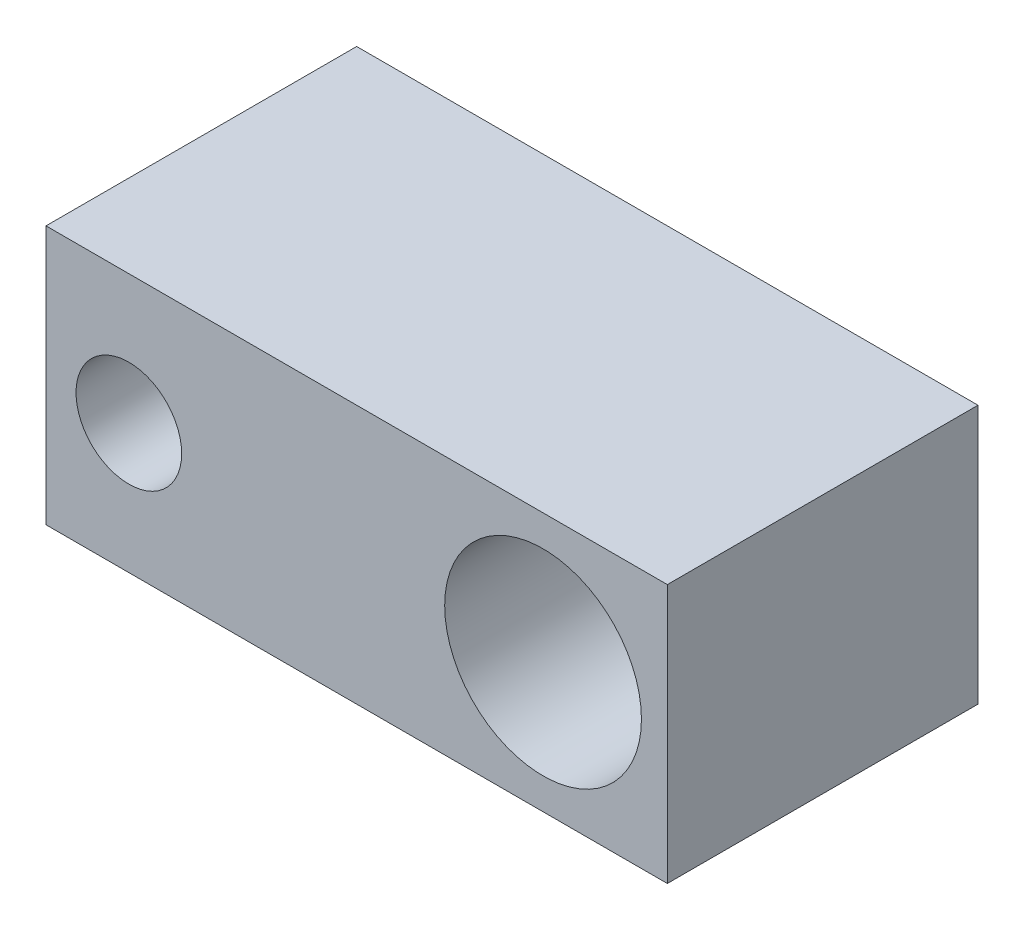
SolidWorks part; units mm, degrees
ref_plane "Front Plane" through (0, 0, 0) normal (0, 0, 1) x (1, 0, 0)
ref_plane "Top Plane" through (0, 0, 0) normal (0, 1, 0) x (1, 0, 0)
ref_plane "Right Plane" through (0, 0, 0) normal (1, 0, 0) x (0, 0, -1)
sketch "Sketch1" plane through (0, 0, 0) normal (0, 0, 1) x (1, 0, 0)
  line L1 (-30, -12.5) -> (30, -12.5)
  line L2 (-30, -12.5) -> (-30, 12.5)
  line L3 (-30, 12.5) -> (30, 12.5)
  line L4 (30, -12.5) -> (30, 12.5)
  line L5 (-30, -12.5) -> (30, 12.5) construction
  line L6 (-30, 12.5) -> (30, -12.5) construction
  circle A0 centre (18, 0) radius 9.5
  circle A1 centre (-22, 0) radius 5.1
  point P0 (0, 0)
  dimension "D2" = 10.2
  dimension "D3" = 19
  dimension "D5" = 8
  dimension "D7" = 12.5
  dimension "D1" = 40
  dimension "D4" = 12
  dimension "D6" = 25
  dimension "D8" = 0
extrude "Boss-Extrude1" add sketch "Sketch1" along normal blind 30
